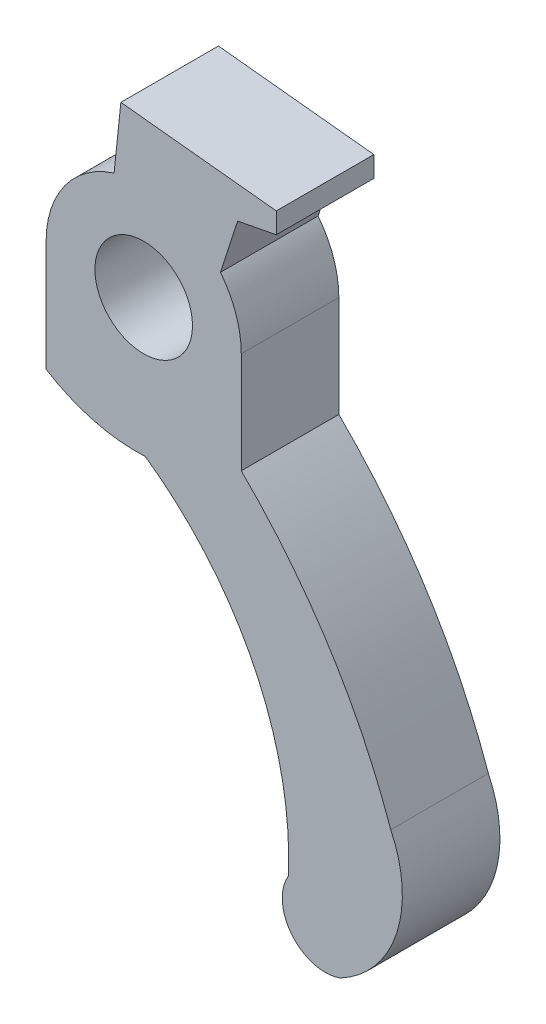
SolidWorks part; units mm, degrees
ref_plane "정면" through (0, 0, 0) normal (0, 0, 1) x (1, 0, 0)
ref_plane "윗면" through (0, 0, 0) normal (0, 1, 0) x (1, 0, 0)
ref_plane "우측면" through (0, 0, 0) normal (1, 0, 0) x (0, 0, -1)
sketch "스케치1" plane through (0, 0, 0) normal (0, 0, 1) x (1, 0, 0)
  line L0 (-6, 0) -> (-6, -6.8217)
  line L1 (4.7215, 3.7024) -> (5.7771, 6.9584)
  line L2 (6, -6.2285) -> (6, 0)
  line L3 (5.7771, 6.9584) -> (8.1523, 7.4162)
  line L4 (8.1523, 7.4162) -> (8.1523, 8.689)
  line L5 (8.1523, 8.689) -> (-1.4044, 9.6904)
  line L6 (-1.4044, 9.6904) -> (-1.8207, 5.7171)
  circle A0 centre (0, 0) radius 3
  arc A1 (6, 0) -> (4.7215, 3.7024) centre (0, 0) ccw
  arc A2 (0.1034, -8.4206) -> (8.8942, -26.364) centre (-11.8731, -25.4132) cw
  arc A3 (15.1924, -20.748) -> (12.0919, -30.1932) centre (8.7422, -23.8621) cw
  arc A4 (15.1924, -20.748) -> (6, -6.2285) centre (-20.6611, -33.2773) ccw
  arc A5 (-6, -6.8217) -> (6, -6.2285) centre (-0.4225, 2.0208) ccw
  arc A6 (8.8942, -26.364) -> (12.0919, -30.1932) centre (11.1619, -27.7201) ccw
  arc A7 (-1.8207, 5.7171) -> (-6, 0) centre (0, 0) ccw
  dimension "D1" = 6
  dimension "D2" = 12
extrude "보스-돌출1" add sketch "스케치1" along normal mid plane 6 contours L0 A5 L2 A1 A0 region at (-4.6581, 3.4052, 0)
extrude "보스-돌출2" add sketch "스케치1<4>" along normal mid plane 6 contours A5 A4 region at (9.8353, -18.3785, 0)
sketch "스케치1<4>" plane through (0, 0, 0) normal (0, 0, 1) x (1, 0, 0) same geometry as "스케치1"
